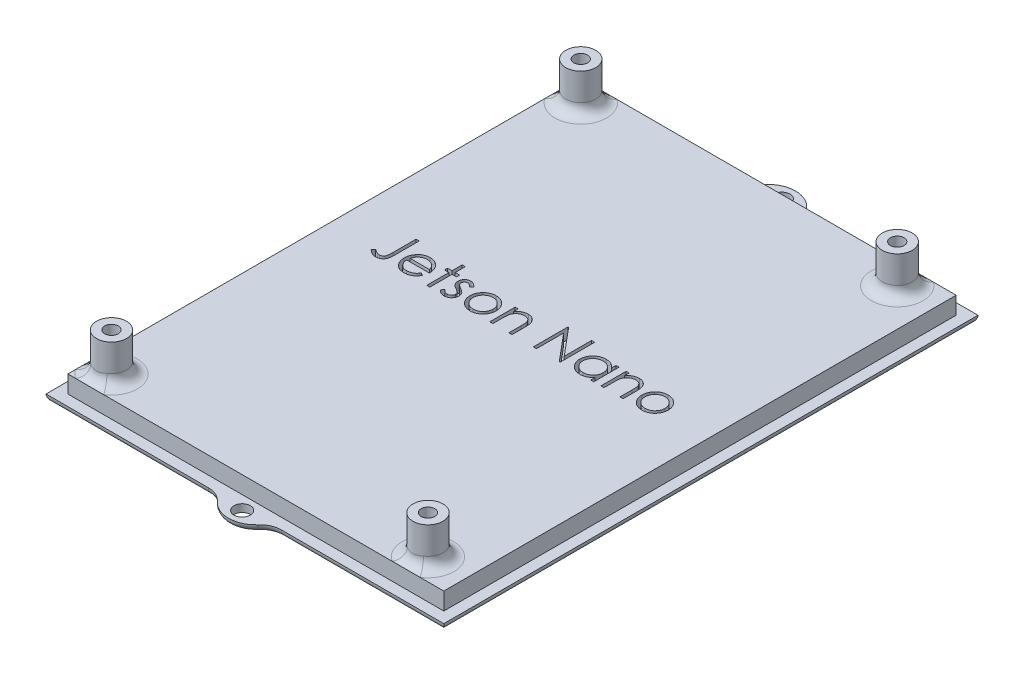
SolidWorks part; units mm, degrees
ref_plane "Front Plane" through (0, 0, 0) normal (0, 0, 1) x (1, 0, 0)
ref_plane "Top Plane" through (0, 0, 0) normal (0, 1, 0) x (1, 0, 0)
ref_plane "Right Plane" through (0, 0, 0) normal (1, 0, 0) x (0, 0, -1)
sketch "Sketch1" plane through (0, 0, 0) normal (0, 1, 0) x (1, 0, 0)
  line L0 (-34.45, 46.95) -> (34.45, 46.95)
  line L5 (-34.45, 46.95) -> (-34.45, -46.95)
  line L6 (-34.45, -46.95) -> (34.45, -46.95)
  line L7 (34.45, 46.95) -> (34.45, -46.95)
  point P11 (-34.45, 0)
  point P12 (0, -46.95)
  dimension "D3" = 93.9
  dimension "D4" = 68.9
extrude "Boss-Extrude1" add sketch "Sketch1" along normal blind 4.575
sketch "Sketch8" plane through (0, 4.575, 0) normal (0, 1, 0) x (1, 0, 0)
  line L2 (-34.45, -46.95) -> (34.45, -46.95) construction
  line L3 (-34.45, 46.95) -> (-34.45, -46.95) construction
  circle A0 centre (-30.45, -42.95) radius 1.25
  circle A1 centre (-30.45, 43.05) radius 1.25
  circle A2 centre (27.55, 43.05) radius 1.25
  circle A3 centre (27.55, -42.95) radius 1.25
  circle A4 centre (-30.45, 43.05) radius 2.75
  circle A5 centre (27.55, 43.05) radius 2.75
  circle A6 centre (27.55, -42.95) radius 2.75
  circle A7 centre (-30.45, -42.95) radius 2.75
  dimension "D3" = 2.5
  dimension "D4" = 1.5
  dimension "D1" = 58
  dimension "D2" = 86
  dimension "D5" = 4
  dimension "D6" = 4
extrude "Boss-Extrude5" add sketch "Sketch8" along normal blind 7
sketch "Sketch3" plane through (0, 4.575, 0) normal (0, 1, 0) x (1, 0, 0)
  circle A5 centre (-30.45, -42.95) radius 1.25 construction
  circle A6 centre (-30.45, 43.05) radius 1.25
  circle A7 centre (27.55, 43.05) radius 1.25
  circle A8 centre (27.55, -42.95) radius 1.25
  circle A9 centre (-30.45, -42.95) radius 1.25
extrude "Cut-Extrude1" cut sketch "Sketch3" against normal offset from surface (3.575 mm away) 1 up to face at (0, 0, 0)
sketch "Sketch9" plane through (0, 0, 0) normal (0, -1, 0) x (1, 0, 0)
  line L8 (-36.45, 48.95) -> (-36.45, -48.95)
  line L9 (-36.45, -48.95) -> (36.45, -48.95)
  line L10 (36.45, -48.95) -> (36.45, 48.95)
  line L11 (36.45, 48.95) -> (-36.45, 48.95)
  line L12 (-36.45, 48.95) -> (-36.45, -48.95)
  line L13 (-36.45, -48.95) -> (36.45, -48.95)
  line L14 (36.45, -48.95) -> (36.45, 48.95)
  line L15 (36.45, 48.95) -> (-36.45, 48.95)
  dimension "D1" = 2
extrude "Boss-Extrude6" add sketch "Sketch9" against normal blind 1.4
sketch "Sketch4" plane through (0, 0, 0) normal (0, 1, 0) x (1, 0, 0)
  line L2 (36.45, -48.95) -> (-36.45, -48.95) construction
  line L4 (34.45, -46.95) -> (-34.45, -46.95) construction
  line L5 (-6.7082, -48.95) -> (6.7082, -48.95)
  arc A3 (-6.7082, -48.95) -> (-3.7268, -50.2833) centre (-6.7082, -52.95) cw
  arc A4 (-3.7268, -50.2833) -> (3.7268, -50.2833) centre (0, -46.95) ccw
  arc A5 (3.7268, -50.2833) -> (6.7082, -48.95) centre (6.7082, -52.95) cw
  dimension "D1" = 5
  dimension "D2" = 4
extrude "Boss-Extrude3" add sketch "Sketch4" along normal blind 1.4
sketch "Sketch10" plane through (0, 1.4, 0) normal (0, 1, 0) x (1, 0, 0)
  line L0 (0, -46.95) -> (0, -51.95) construction
  line L1 (34.45, -46.95) -> (-34.45, -46.95) construction
  arc A0 (-3.7268, -50.2833) -> (3.7268, -50.2833) centre (0, -46.95) ccw construction
  circle A1 centre (0, -49.45) radius 1.5
  dimension "D1" = 3
extrude "Cut-Extrude3" cut sketch "Sketch10" against normal up to next
mirror "Mirror1" about plane through (0, 0, 0) normal (0, 0, 1) of "Cut-Extrude3", "Boss-Extrude3"
sketch "Sketch5" plane through (0, 4.575, 0) normal (0, 1, 0) x (1, 0, 0)
  line L0 (-30, 0) -> (30, 0) construction
  text T0 "Jetson Nano" font "Century Gothic" height in points 24
  point P6 (0, 0)
  dimension "D1" = 60
extrude "Cut-Extrude2" cut sketch "Sketch5" against normal blind 2
fillet "Fillet1" radius 1.4 12 edges at (36.45, 0, 0) (21.5791, 0, -48.95) (5.0752, 0, -49.2985) (0, 0, -51.95) (-5.0752, 0, -49.2985) (-21.5791, 0, -48.95) (-36.45, 0, 0) (-21.5791, 0, 48.95) (-5.0752, 0, 49.2985) (0, 0, 51.95) (5.0752, 0, 49.2985) (21.5791, 0, 48.95)
fillet "Fillet2" radius 2 4 edges at (-30.45, 4.575, 45.7) (-30.45, 4.575, -40.3) (27.55, 4.575, -40.3) (27.55, 4.575, 45.7)
